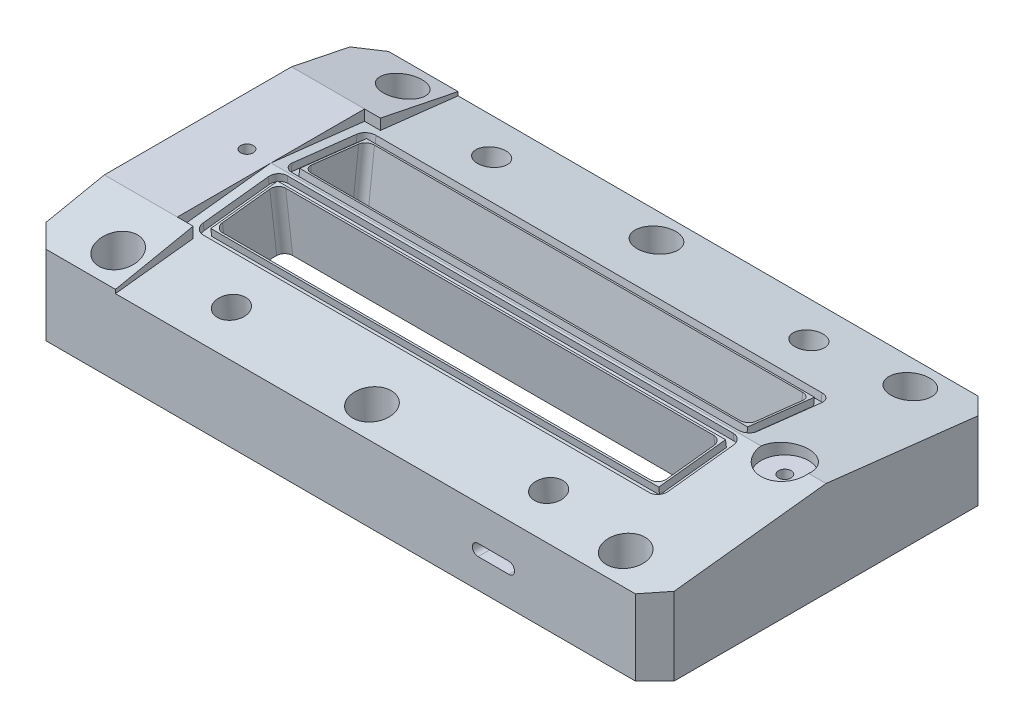
SolidWorks part; units mm, degrees
material "Custom Plastic"
ref_plane "Front Plane" through (0, 0, 0) normal (0, 0, 1) x (1, 0, 0)
ref_plane "Top Plane" through (0, 0, 0) normal (0, 1, 0) x (1, 0, 0)
ref_plane "Right Plane" through (0, 0, 0) normal (1, 0, 0) x (0, 0, -1)
sketch "Sketch1" plane through (0, 0, 0) normal (0, 1, 0) x (1, 0, 0)
  line L1 (0, 0) -> (198, 0)
  line L2 (0, 0) -> (0, 108)
  line L3 (0, 108) -> (198, 108)
  line L4 (198, 0) -> (198, 108)
  dimension "D1" = 198
  dimension "D2" = 108
extrude "Boss-Extrude1" add sketch "Sketch1" along normal blind 30
ref_plane "Left" through (198, 0, 0) normal (1, 0, 0) x (0, 0, -1)
ref_plane "Bot" through (0, 30, 0) normal (0, 1, 0) x (1, 0, 0)
ref_plane "der loco" through (0, 0, -52) normal (0, 0, -1) x (-1, 0, 0)
sketch "Sketch4" plane through (0, 0, 0) normal (0, 1, 0) x (1, 0, 0)
  line L0 (0, 108) -> (0, 0) construction
  line L1 (8.5, 31.5) -> (189.5, 31.5)
  line L2 (8.5, 31.5) -> (8.5, 76.5)
  line L3 (8.5, 76.5) -> (189.5, 76.5)
  line L4 (189.5, 31.5) -> (189.5, 76.5)
  line L5 (0, 0) -> (198, 0) construction
  dimension "D1" = 181
  dimension "D2" = 8.5
  dimension "D3" = 45
  dimension "D4" = 31.5
extrude "Cut-Extrude2" cut sketch "Sketch4" along normal blind 10 contours L2 L1 L4 L3
ref_plane "Plane32" through (0, 10, 0) normal (0, -1, 0) x (-1, 0, 0)
sketch "Sketch5" plane through (198, 0, 0) normal (1, 0, 0) x (0, 0, -1)
  line L0 (54, 30) -> (108, 23.8284)
  line L1 (0, 30) -> (108, 30) construction
  line L2 (108, 23.8284) -> (108, 30)
  line L3 (108, 30) -> (54, 30)
  line L4 (108, 30) -> (108, 0) construction
  dimension "D1" = 6.52
  dimension "D2" = 54
extrude "Cut-Extrude3" cut sketch "Sketch5" against normal blind 170
ref_plane "Plane24" through (0, 10, 0) normal (0, -1, 0) x (-1, 0, 0)
sketch "Sketch53" plane through (0, 10, 0) normal (0, -1, 0) x (-1, 0, 0)
  line L0 (-8.5, 51.5) -> (-8.5, 31.5)
  line L1 (-8.5, 76.5) -> (-8.5, 31.5) construction
  line L2 (-8.5, 31.5) -> (-39.5, 31.5)
  line L3 (-8.5, 31.5) -> (-189.5, 31.5) construction
  line L4 (-39.5, 31.5) -> (-8.5, 51.5)
  line L5 (-8.5, 54) -> (-189.5, 54) construction
  line L6 (-189.5, 31.5) -> (-189.5, 76.5) construction
  line L7 (-8.5, 56.5) -> (-8.5, 76.5)
  line L8 (-8.5, 76.5) -> (-39.5, 76.5)
  line L9 (-39.5, 76.5) -> (-8.5, 56.5)
  line L10 (-99, 76.5) -> (-99, 31.5) construction
  line L11 (-8.5, 76.5) -> (-189.5, 76.5) construction
  line L12 (-8.5, 31.5) -> (-189.5, 31.5) construction
  line L13 (-158.5, 76.5) -> (-189.5, 56.5)
  line L14 (-189.5, 76.5) -> (-158.5, 76.5)
  line L15 (-189.5, 56.5) -> (-189.5, 76.5)
  line L16 (-158.5, 31.5) -> (-189.5, 51.5)
  line L17 (-189.5, 31.5) -> (-158.5, 31.5)
  line L18 (-189.5, 51.5) -> (-189.5, 31.5)
  dimension "D1" = 31
  dimension "D2" = 20
extrude "Boss-Extrude11" add sketch "Sketch53" along normal up to surface (10 mm away) up to face at (99, 0, -54)
ref_plane "izq loco" through (0, 0, -57) normal (0, 0, -1) x (-1, 0, 0)
sketch "Sketch18" plane through (198, 0, 0) normal (1, 0, 0) x (0, 0, -1)
  line L0 (0, 23.8284) -> (0, 30)
  line L1 (0, 30) -> (0, 0) construction
  line L2 (0, 30) -> (54, 30)
  line L3 (54, 30) -> (0, 23.8284)
  line L4 (0, 30) -> (54, 30) construction
  dimension "D1" = 54
  dimension "D2" = 6.52
extrude "Cut-Extrude12" cut sketch "Sketch18" against normal up to surface (170 mm away) up to face at (28, 27.9428, -90)
sketch "Sketch60" plane through (0, 0, 0) normal (0, 1, 0) x (1, 0, 0)
  point P0 (8.5, 31.5)
  point P1 (39.5, 31.5)
  point P2 (8.5, 76.5)
  point P6 (39.5, 76.5)
  dimension "D1" = 20
  dimension "D2" = 31
  dimension "D3" = 20
  dimension "D4" = 31
ref_axis "Axis6" through (8.5, 0, -31.5) along (1, 0, 0)
sketch "Sketch69" plane through (0, 10, 0) normal (0, -1, 0) x (-1, 0, 0)
  point P0 (-39.5, 56.5)
  point P1 (-8.5, 51.5)
  point P2 (-38.5, 51.5)
  point P3 (-8.5, 56.5)
  dimension "D1" = 31
  dimension "D2" = 20
  dimension "D3" = 20
  dimension "D4" = 30
sketch "der loco axis" plane through (0, 0, -52) normal (0, 0, -1) x (-1, 0, 0)
  point P0 (-8.5, 8.5)
  point P1 (-38.5, 8.5)
  dimension "D1" = 1.5
sketch "izq loco axis" plane through (0, 0, -57) normal (0, 0, -1) x (-1, 0, 0)
  line L0 (-39.5, 0) -> (-39.5, 10) construction
  line L1 (-8.5, 0) -> (-8.5, 10) construction
  point P0 (-8.5, 8.4959)
  point P1 (-39.5, 8.4959)
  dimension "D1" = 1.5041
ref_plane "Plane3" through (0, 35.7052, -4.0807) normal (0, 0.9935, -0.1136) x (1, 0, 0)
ref_axis "Axis8" through (39.5, 0, -76.5) along (-1, 0, 0)
ref_axis "Axis9" through (8.5, 8.4959, -57) along (1, 0, 0)
ref_axis "Axis10" through (38.5, 8.5, -52) along (-1, 0, 0)
ref_plane "Izq bueno" through (0, 28.0127, -12.2048) normal (0, 0.9168, -0.3994) x (1, 0, 0)
sketch "Izq" plane through (0, 28.0127, -12.2048) normal (0, 0.9168, -0.3994) x (1, 0, 0)
  line L0 (8.5, 48.8622) -> (29.5, 70.1326)
  line L1 (29.5, 70.1326) -> (8.5, 70.1326)
  line L2 (8.5, 70.1326) -> (8.5, 48.8622)
  dimension "D1" = 21
extrude "Cut-Extrude28" cut sketch "Izq" against normal blind 14.5
ref_plane "Der bueno" through (0, -11.1449, -4.6211) normal (0, 0.9237, 0.383) x (1, 0, 0)
sketch "Der" plane through (0, -11.1449, -4.6211) normal (0, 0.9237, 0.383) x (1, 0, 0)
  line L0 (8.5, 51.2902) -> (29.5, 29.0979)
  line L1 (29.5, 29.0979) -> (8.5, 29.0979)
  line L2 (8.5, 29.0979) -> (8.5, 51.2902)
  dimension "D1" = 21
extrude "Cut-Extrude29" cut sketch "Der" against normal blind 14.5
sketch "Sketch97" plane through (0, 0, 0) normal (0, 1, 0) x (1, 0, 0)
  line L0 (8.5, 57.5) -> (29.5, 76.5)
  line L1 (29.5, 76.5) -> (158.5, 76.5)
  line L3 (158.5, 31.5) -> (29.5, 31.5)
  line L4 (29.5, 31.5) -> (8.5, 51.5)
  line L5 (8.5, 51.5) -> (8.5, 57.5)
  line L7 (158.5, 76.5) -> (189.5, 56.5)
  line L8 (189.5, 56.5) -> (189.5, 51.5)
  line L9 (189.5, 51.5) -> (158.5, 31.5)
  line L10 (39.5, 76.5) -> (158.5, 76.5) construction
  dimension "D1" = 6
extrude "Cut-Extrude40" cut sketch "Sketch97" along normal up to surface (10 mm away) up to face at (99, 10, -54)
ref_axis "Axis11" through (99, 0, -108) along (0, 0, 1)
ref_plane "Plane33" through (99, 0, 0) normal (1, 0, 0) x (0, 0, -1)
mirror "Mirror2" about plane through (99, 0, 0) normal (1, 0, 0) of "Cut-Extrude29", "Cut-Extrude40", "Cut-Extrude28"
sketch "Sketch6" plane through (0, 35.7052, -4.0807) normal (0, 0.9935, -0.1136) x (1, 0, 0)
  line L0 (28, 50.2442) -> (198, 50.2442) construction
  line L1 (28.9, 77.6442) -> (169.5, 77.6442)
  line L2 (25.9, 74.6442) -> (25.9, 54.0442)
  line L3 (28.9, 51.0442) -> (169.5, 51.0442)
  line L4 (172.5, 74.6442) -> (172.5, 54.0442)
  line L7 (28.6, 53.7442) -> (169.8, 53.7442)
  line L8 (28.6, 53.7442) -> (28.6, 74.9442)
  line L9 (28.6, 74.9442) -> (169.8, 74.9442)
  line L10 (169.8, 53.7442) -> (169.8, 74.9442)
  line L13 (198, 50.2442) -> (198, 104.5958) construction
  arc A0 (169.5, 77.6442) -> (172.5, 74.6442) centre (169.5, 74.6442) cw
  arc A1 (169.5, 51.0442) -> (172.5, 54.0442) centre (169.5, 54.0442) ccw
  arc A2 (25.9, 54.0442) -> (28.9, 51.0442) centre (28.9, 54.0442) ccw
  arc A3 (28.9, 77.6442) -> (25.9, 74.6442) centre (28.9, 74.6442) ccw
  dimension "D1" = 3
  dimension "D2" = 146.6
  dimension "D3" = 20.6
  dimension "D4" = 25.5
  dimension "D5" = 3.5
  dimension "D6" = 2.7
  dimension "D7" = 2.7
  dimension "D8" = 2.7
  dimension "D9" = 2.7
sketch "Sketch7" plane through (0, 0, 0) normal (1, 0, 0) x (0, 0, -1)
  line L1 (108, 30) -> (108, 0) construction
  line L2 (108, 30) -> (0, 30) construction
  line L3 (108, 30) -> (108, 25)
  line L5 (108, 25) -> (83.5051, 30)
  line L6 (108, 30) -> (83.5051, 30)
  line L7 (0, 25) -> (0, 30)
  line L8 (0, 30) -> (0, 0) construction
  line L9 (0, 30) -> (24.4949, 30)
  line L10 (24.4949, 30) -> (0, 25)
  dimension "D1" = 25
  dimension "D2" = 25
  dimension "D3" = 25
  dimension "D4" = 25
extrude "Cut-Extrude5" cut sketch "Sketch7" along normal up to vertex (28 mm away) up to point (28, 30, 0)
sketch "Sketch9" plane through (0, 30, 0) normal (0, 1, 0) x (1, 0, 0)
  line L0 (0, 83.5051) -> (0, 24.4949) construction
  circle A0 centre (15.45, 54) radius 8
  point P6 (0, 54)
  dimension "D1" = 16
  dimension "D2" = 15.45
sketch "Sketch12" plane through (0, 30, 0) normal (0, 1, 0) x (1, 0, 0)
  line L0 (0, 83.5051) -> (0, 108) construction
  line L2 (28, 108) -> (0, 108) construction
  line L3 (28, 0) -> (0, 0) construction
  circle A0 centre (19.7, 98.85) radius 3.15
  circle A1 centre (99.7, 9.15) radius 3.15
  circle A2 centre (179.7, 9.15) radius 3.15
  circle A3 centre (19.7, 9.15) radius 3.15
  circle A4 centre (99.7, 98.85) radius 3.15
  circle A5 centre (179.7, 98.85) radius 3.15
  dimension "D2" = 6.3
  dimension "D3" = 19.7
  dimension "D7" = 80
  dimension "D9" = 80
  dimension "D10" = 9.15
  dimension "D11" = 9.15
extrude "Cut-Extrude9" cut sketch "Sketch12" against normal through all
sketch "Sketch13" plane through (0, 35.7052, -4.0807) normal (0, 0.9935, -0.1136) x (1, 0, 0)
  line L0 (28, 50.2442) -> (28, 104.5958) construction
  line L1 (28, 104.5958) -> (198, 104.5958) construction
  line L2 (198, 50.2442) -> (198, 104.5958) construction
  circle A0 centre (51.5, 91.5958) radius 4.5
  circle A1 centre (151.5, 91.5958) radius 4.5
  dimension "D1" = 9
  dimension "D4" = 9
  dimension "D2" = 23.5
  dimension "D3" = 13
  dimension "D5" = 46.5
extrude "Cut-Extrude10" cut sketch "Sketch13" against normal blind 16.5
ref_plane "Plane8" through (0, 24, 4.899) normal (0, 0.9798, 0.2) x (1, 0, 0)
sketch "Sketch14" plane through (0, 23.1877, 5.6057) normal (0, 0.9935, 0.1136) x (1, 0, 0)
  line L0 (28, 5.7752) -> (0, 5.7752) construction
  line L1 (28, 59.9937) -> (28, 112.9437) construction
  line L2 (198, 5.7752) -> (198, 30.6795) construction
  circle A0 centre (51.5, 18.7752) radius 4.5
  circle A1 centre (151.5, 18.7752) radius 4.5
  dimension "D1" = 9
  dimension "D2" = 9
  dimension "D3" = 13
  dimension "D4" = 23.5
  dimension "D5" = 46.5
extrude "Cut-Extrude11" cut sketch "Sketch14" against normal blind 16.5
ref_plane "Plane9" through (0, 23.5211, 2.6882) normal (0, 0.9935, 0.1136) x (1, 0, 0)
sketch "Sketch23" plane through (0, 23.5211, 2.6882) normal (0, 0.9935, 0.1136) x (1, 0, 0)
  line L0 (28, 57.0572) -> (198, 57.0572) construction
  line L1 (28.9, 56.2572) -> (169.5, 56.2572)
  line L2 (25.9, 53.2572) -> (25.9, 32.6572)
  line L3 (28.9, 29.6572) -> (169.5, 29.6572)
  line L4 (172.5, 53.2572) -> (172.5, 32.6572)
  line L7 (28.6, 53.5572) -> (169.8, 53.5572)
  line L8 (28.6, 53.5572) -> (28.6, 32.3572)
  line L9 (28.6, 32.3572) -> (169.8, 32.3572)
  line L10 (169.8, 53.5572) -> (169.8, 32.3572)
  line L12 (198, 2.7057) -> (198, 57.0572) construction
  arc A0 (169.5, 56.2572) -> (172.5, 53.2572) centre (169.5, 53.2572) cw
  arc A1 (169.5, 29.6572) -> (172.5, 32.6572) centre (169.5, 32.6572) ccw
  arc A2 (25.9, 32.6572) -> (28.9, 29.6572) centre (28.9, 32.6572) ccw
  arc A3 (28.9, 56.2572) -> (25.9, 53.2572) centre (28.9, 53.2572) ccw
  point P10 (172.5, 56.2572)
  point P15 (25.9, 29.6572)
  point P18 (25.9, 56.2572)
  dimension "D5" = 3
  dimension "D1" = 146.6
  dimension "D2" = 20.6
  dimension "D3" = 3.5
  dimension "D4" = 25.5
  dimension "D6" = 2.7
  dimension "D7" = 2.7
  dimension "D8" = 2.7
  dimension "D9" = 2.7
sketch "Sketch41" plane through (0, 0, 0) normal (0, 1, 0) x (1, 0, 0)
  line L0 (198, 0) -> (198, 108) construction
  line L1 (198, 108) -> (0, 108) construction
  line L2 (0, 0) -> (198, 0) construction
  circle A0 centre (139.5, 9) radius 2.9
  circle A1 centre (139.5, 99) radius 2.9
  dimension "D1" = 5.8
  dimension "D4" = 5.8
  dimension "D2" = 58.5
  dimension "D3" = 58.5
  dimension "D5" = 9
  dimension "D6" = 9
extrude "Cut-Extrude21" cut sketch "Sketch41" along normal blind 7
sketch "Sketch42" plane through (0, 0, 0) normal (0, 0, 1) x (1, 0, 0)
  line L0 (198, 23.8284) -> (198, 0) construction
  line L5 (0, 0) -> (198, 0) construction
  line L6 (142.3, 12.8) -> (152, 12.8)
  line L7 (142.3, 9.2) -> (152, 9.2)
  arc A0 (142.3, 12.8) -> (142.3, 9.2) centre (142.3, 11) ccw
  arc A2 (152, 12.8) -> (152, 9.2) centre (152, 11) cw
  dimension "D2" = 1.8
  dimension "D3" = 1.8
  dimension "D1" = 9.7
  dimension "D5" = 46
  dimension "D6" = 11
extrude "Cut-Extrude22" cut sketch "Sketch42" against normal blind 10
ref_plane "Plane19" through (0, 0, -108) normal (0, 0, -1) x (-1, 0, 0)
sketch "Sketch43" plane through (0, 0, -108) normal (0, 0, -1) x (-1, 0, 0)
  line L0 (-55.7, 11) -> (-46, 11) construction
  line L1 (-55.7, 12.8) -> (-46, 12.8)
  line L2 (-55.7, 9.2) -> (-46, 9.2)
  line L3 (-198, 0) -> (0, 0) construction
  line L4 (0, 25) -> (0, 0) construction
  arc A0 (-55.7, 12.8) -> (-55.7, 9.2) centre (-55.7, 11) ccw
  arc A1 (-46, 9.2) -> (-46, 12.8) centre (-46, 11) ccw
  point P2 (-50.85, 11)
  dimension "D2" = 1.8
  dimension "D1" = 9.7
  dimension "D3" = 11
  dimension "D4" = 46
extrude "Cut-Extrude23" cut sketch "Sketch43" against normal blind 10
extrude "Cut-Extrude32" cut sketch "Sketch6" against normal blind 2.3
extrude "Cut-Extrude33" cut sketch "Sketch23" against normal blind 2.3
sketch "Sketch83" plane through (0, 23.5211, 2.6882) normal (0, 0.9935, 0.1136) x (1, 0, 0)
  line L0 (28.6, 53.5572) -> (28.6, 32.3572) construction
  line L1 (31.7, 52.9572) -> (166.7, 52.9572)
  line L2 (29.2, 50.4572) -> (29.2, 35.4572)
  line L3 (31.7, 32.9572) -> (166.7, 32.9572)
  line L4 (169.2, 50.4572) -> (169.2, 35.4572)
  line L5 (169.8, 53.5572) -> (28.6, 53.5572) construction
  arc A0 (166.7, 32.9572) -> (169.2, 35.4572) centre (166.7, 35.4572) ccw
  arc A1 (166.7, 52.9572) -> (169.2, 50.4572) centre (166.7, 50.4572) cw
  arc A2 (29.2, 35.4572) -> (31.7, 32.9572) centre (31.7, 35.4572) ccw
  arc A3 (31.7, 52.9572) -> (29.2, 50.4572) centre (31.7, 50.4572) ccw
  point P12 (169.2, 52.9572)
  point P15 (29.2, 32.9572)
  point P18 (29.2, 52.9572)
  point P19 (169.2, 42.9572)
  dimension "D5" = 2.5
  dimension "D1" = 140
  dimension "D2" = 20
  dimension "D3" = 0.6
  dimension "D4" = 0.6
extrude "Cut-Extrude34" cut sketch "Sketch83" against normal blind 55.4
sketch "Sketch84" plane through (0, 35.7052, -4.0807) normal (0, 0.9935, -0.1136) x (1, 0, 0)
  line L1 (31.7, 54.3442) -> (166.7, 54.3442)
  line L2 (29.2, 56.8442) -> (29.2, 71.8442)
  line L3 (31.7, 74.3442) -> (166.7, 74.3442)
  line L4 (169.2, 56.8442) -> (169.2, 71.8442)
  line L6 (169.8, 53.7442) -> (169.8, 74.9442) construction
  line L8 (28.6, 53.7442) -> (169.8, 53.7442) construction
  arc A0 (166.7, 54.3442) -> (169.2, 56.8442) centre (166.7, 56.8442) ccw
  arc A1 (166.7, 74.3442) -> (169.2, 71.8442) centre (166.7, 71.8442) cw
  arc A2 (29.2, 71.8442) -> (31.7, 74.3442) centre (31.7, 71.8442) cw
  arc A3 (31.7, 54.3442) -> (29.2, 56.8442) centre (31.7, 56.8442) cw
  point P10 (169.2, 54.3442)
  point P13 (169.2, 74.3442)
  point P16 (29.2, 74.3442)
  point P19 (169.2, 64.3442)
  dimension "D5" = 2.5
  dimension "D1" = 140
  dimension "D2" = 20
  dimension "D3" = 0.6
  dimension "D4" = 0.6
extrude "Cut-Extrude35" cut sketch "Sketch84" against normal blind 55.4
sketch "Sketch85" plane through (0, 30, 0) normal (0, 1, 0) x (1, 0, 0)
  line L0 (0, 101.9) -> (6.1, 108)
  line L1 (0, 83.5051) -> (0, 108) construction
  line L2 (28, 108) -> (0, 108) construction
  line L3 (6.1, 108) -> (0, 108)
  line L4 (0, 108) -> (0, 101.9)
  line L5 (0, 0) -> (6.1, 0)
  line L6 (28, 0) -> (0, 0) construction
  line L7 (6.1, 0) -> (0, 6.1)
  line L8 (0, 0) -> (0, 24.4949) construction
  line L9 (0, 6.1) -> (0, 0)
  line L10 (198, 6.1) -> (191.9, 0)
  line L11 (198, 0) -> (198, 54) construction
  line L12 (28, 0) -> (198, 0) construction
  line L13 (191.9, 0) -> (198, 0)
  line L14 (198, 0) -> (198, 6.1)
  line L15 (198, 108) -> (191.9, 108)
  line L16 (28, 108) -> (198, 108) construction
  line L17 (191.9, 108) -> (198, 101.9)
  line L18 (198, 54) -> (198, 108) construction
  line L19 (198, 101.9) -> (198, 108)
  dimension "D1" = 6.1
  dimension "D2" = 6.1
  dimension "D3" = 6.1
  dimension "D4" = 6.1
  dimension "D5" = 6.1
  dimension "D6" = 6.1
  dimension "D7" = 6.1
extrude "Cut-Extrude36" cut sketch "Sketch85" against normal blind 55.4
sketch "Sketch90" plane through (0, 30, 0) normal (0, 1, 0) x (1, 0, 0)
  circle A0 centre (19.7, 9.15) radius 6.1
  circle A1 centre (99.7, 9.15) radius 6.1
  circle A2 centre (179.7, 9.15) radius 6.1
  circle A3 centre (99.7, 98.85) radius 6.1
  circle A4 centre (179.7, 98.85) radius 6.1
  circle A5 centre (19.7, 98.85) radius 6.1
  circle A6 centre (179.7, 98.85) radius 3.15 construction
  circle A7 centre (99.7, 98.85) radius 3.15 construction
  dimension "D1" = 12.2
  dimension "D2" = 3
  dimension "D3" = 2
extrude "Cut-Extrude38" cut sketch "Sketch90" against normal blind 17
sketch "Sketch96" plane through (0, 0, 0) normal (0, 1, 0) x (1, 0, 0)
  line L0 (28, 54) -> (198, 54) construction
  line L1 (198, 6.1) -> (198, 101.9) construction
  circle A0 centre (15.45, 54) radius 2
  circle A1 centre (185, 54) radius 2
  dimension "D1" = 4
  dimension "D2" = 4
  dimension "D3" = 13
extrude "Cut-Extrude39" cut sketch "Sketch96" along normal through all
sketch "Sketch98" plane through (0, 30, 0) normal (0, 1, 0) x (1, 0, 0)
  circle A0 centre (185, 54) radius 7.5
  dimension "D1" = 15
extrude "Cut-Extrude41" cut sketch "Sketch98" against normal blind 4
sketch "Sketch99" plane through (198, 0, 0) normal (1, 0, 0) x (0, 0, -1)
  line L0 (57.4774, 29.6026) -> (78.5402, 27.1953) construction
  line L1 (54, -84.21) -> (68.0088, 28.3989) construction
  line L2 (54, -84.21) -> (123.3982, -92.1415) construction
  line L3 (54, 30) -> (101.9, 24.5255) construction
  line L4 (54, -84.21) -> (-15.3982, -92.1415) construction
  line L5 (6.1, 24.5255) -> (54, 30) construction
  line L6 (52.8612, -84.21) -> (39.9912, 28.3989) construction
  line L7 (-15.85, -84.21) -> (123.85, -84.21) construction
  line L8 (54, -84.21) -> (39.9912, 28.3989) construction
  line L9 (32.5397, 27.5473) -> (47.4427, 29.2506) construction
  line L10 (55.1388, -84.21) -> (68.0088, 28.3989) construction
  circle A0 centre (54, -84.21) radius 69.85
  point P19 (39.9912, 28.3989)
  dimension "D1" = 139.7
  dimension "D2" = 84.21
  dimension "D3" = 89.429
  dimension "D4" = 89.429
  dimension "D5" = 1.1388
sketch "Sketch100" plane through (198, 0, 0) normal (1, 0, 0) x (0, 0, -1)
  line L0 (24.4949, 30) -> (24.4949, 26.6279)
  line L1 (6.1, 24.5255) -> (54, 30) construction
  line L2 (24.4949, 26.6279) -> (54, 30)
  line L3 (54, 30) -> (54.9321, 29.8935) construction
  line L4 (54, 30) -> (24.4949, 30)
extrude "Cut-Extrude42" cut sketch "Sketch100" against normal blind 175
sketch "Sketch101" plane through (198, 0, 0) normal (1, 0, 0) x (0, 0, -1)
  line L0 (54, 30) -> (83.5051, 30)
  line L1 (83.5051, 30) -> (83.5051, 26.6279)
  line L2 (81.0855, 26.9044) -> (108, 23.8284) construction
  line L3 (83.5051, 26.6279) -> (54, 30)
extrude "Cut-Extrude43" cut sketch "Sketch101" against normal blind 175
